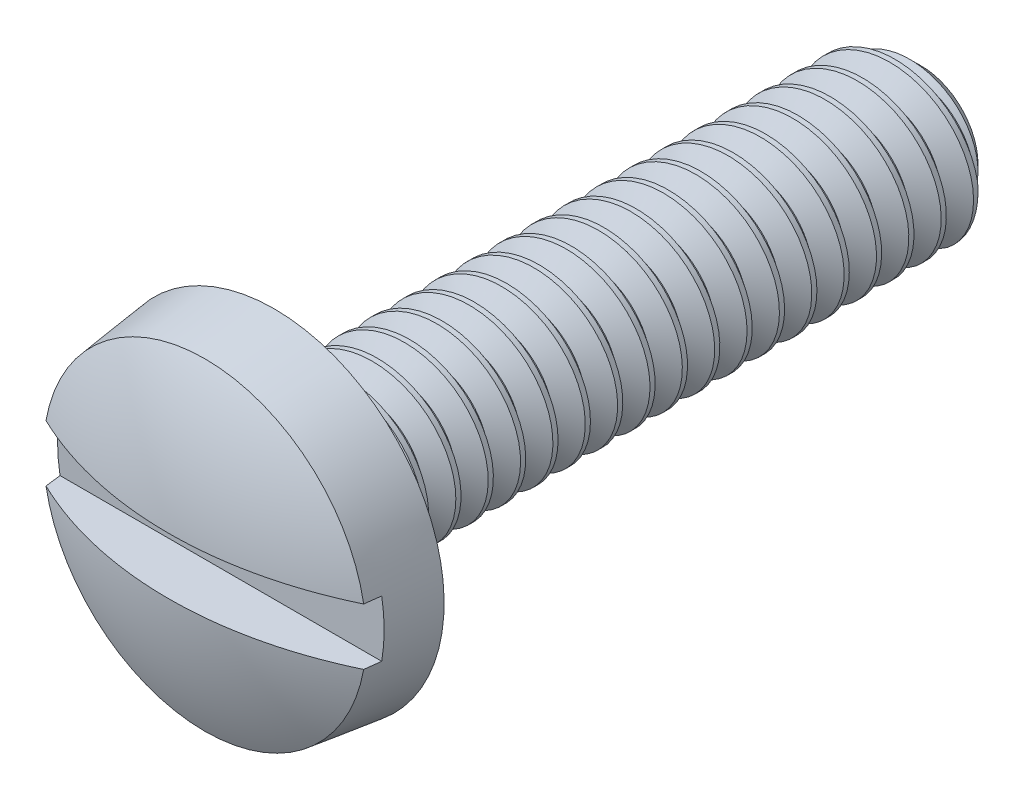
SolidWorks part; units mm, degrees
ref_plane "Front" through (0, 0, 0) normal (0, 0, 1) x (1, 0, 0)
ref_plane "Top" through (0, 0, 0) normal (0, 1, 0) x (1, 0, 0)
ref_plane "Right" through (0, 0, 0) normal (1, 0, 0) x (0, 0, -1)
sketch "Sketch1" plane through (0, 0, 0) normal (0, 0, 1) x (1, 0, 0)
  circle A0 centre (0, 0) radius 6.6675
  dimension "Head Dia" = 13.335
extrude "Extrude3" add sketch "Sketch1" along normal blind 4.191
sketch "Sketch11" plane through (0, 0, 0) normal (1, 0, 0) x (0, 0, -1)
  line L0 (0, 0) -> (-4.445, 0) construction
  line L3 (0, 6.6675) -> (-4.191, 6.6675) construction
  line L4 (-4.191, 6.6675) -> (-4.191, -6.6675) construction
  line L5 (-4.445, 6.9342) -> (0, 6.9342)
  line L7 (0, 6.9342) -> (0, 6.6675)
  line L8 (-2.7242, 6.333) -> (0, 6.6675)
  line L9 (0, -6.6675) -> (0, 6.6675) construction
  line L13 (-4.191, 0) -> (-4.445, 0)
  line L14 (-4.445, 0) -> (-4.445, 6.9342)
  arc A0 (-2.7242, 6.333) -> (-4.191, 0) centre (10.2136, 0) ccw
  dimension "D2" = 1.4668
  dimension "D1" = 7
  dimension "D3" = 0.254
  dimension "D5" = 0.2667
revolve "Cut-Revolve3" cut sketch "Sketch11" angle 360 about L0
sketch "Sketch4" plane through (0, 0, 0) normal (1, 0, 0) x (0, 0, -1)
  line L0 (0, 0) -> (25.4, 0)
  line L3 (25.4, 0) -> (25.4, 3.175)
  line L4 (25.4, 3.175) -> (0, 3.175)
  line L6 (0, 3.175) -> (0, 0)
  line L9 (25.4, 3.175) -> (25.4, -3.175) construction
  dimension "dia" = 6.35
  dimension "length" = 25.4
revolve "Revolve1" add sketch "Sketch4" angle 360 about L0
sketch "Sketch13" plane through (0, 0, -25.4) normal (0, 0, -1) x (-1, 0, 0)
  circle A2 centre (0, 0) radius 3.175
curve "Helix/Spiral1" pitch 1.27 height 29.591 radius 3.175 centre (0, 0, -25.4) axis (0, 0, 1) start towards (1, 0, 0)
chamfer "Chamfer2" distance 0.9525 angle 45 1 edges at (3.175, 0, -25.4)
sketch "Sketch14" plane through (0, 0, 0) normal (1, 0, 0) x (0, 0, -1)
  line L0 (25.4, 3.2147) -> (26.5112, 3.2147)
  line L1 (26.5112, 3.2147) -> (26.035, 2.3555)
  line L2 (26.035, 2.3555) -> (25.8762, 2.3555)
  line L3 (25.8762, 2.3555) -> (25.4, 3.2147)
  line L4 (25.6381, 2.7851) -> (26.2731, 2.7851) construction
  dimension "D1" = 0.1588
  dimension "D2" = 58
  dimension "D3" = 0.635
  dimension "D4" = 0.0397
sweep "Cut-Sweep1" cut profiles "Sketch14" path "Helix/Spiral1"
ref_plane "Plane1" through (0, 0, 12.7) normal (0, 0, -1) x (-1, 0, 0)
sketch "Sketch29" [suppressed] plane through (0, 0, 28.575) normal (0, 0, -1) x (-1, 0, 0)
  circle A0 centre (0, 0) radius 1.7526 construction
  circle A1 centre (0, 0) radius 1.7526
  point P3 (0, -1.7526)
  point P4 (0, 1.7526)
extrude "Extrude11" [suppressed] add sketch "Sketch29" against normal up to surface (28.575 mm away) up to plane "Front"
ref_plane "Plane2" through (0, 0, 4.191) normal (0, 0, 1) x (1, 0, 0)
sketch "Sketch26" plane through (0, 0, 0) normal (0, 0, 1) x (1, 0, 0)
  circle A1 centre (0, 0) radius 0.5461
  dimension "D1" = 1.0922
extrude "Extrude13" add sketch "Sketch26" along normal up to surface (4.1806 mm away)
sketch "Sketch31" plane through (0, 0, 4.191) normal (0, 0, 1) x (1, 0, 0)
  line L0 (-6.6675, 1.1112) -> (6.6675, -1.1112) construction
  line L1 (-6.6675, 1.1112) -> (6.6675, 1.1113)
  line L2 (-6.6675, 1.1112) -> (-6.6675, -1.1113)
  line L3 (-6.6675, -1.1113) -> (6.6675, -1.1112)
  line L4 (6.6675, 1.1113) -> (6.6675, -1.1112)
  circle A0 centre (0, 0) radius 6.6675 construction
  dimension "D1" = 2.2225
extrude "Extrude15" cut sketch "Sketch31" against normal blind 2.0955
sketch "Sketch18" plane through (0, 0, 0) normal (1, 0, 0) x (0, 0, -1)
  line L1 (25.4, 3.175) -> (0, 3.175) construction
  point P0 (23.495, -3.175)
  point P1 (24.13, 3.175)
  point P2 (-4.191, 1.1113)
  dimension "D1" = 1.27
  dimension "D2" = 1.905
equation "\"D3@Helix/Spiral1\" = \"Length@Sketch4\" + \"Head Ht@Extrude3\""
equation "\"D1@Sketch14\" = \"D4@Helix/Spiral1\" * .125"
equation "\"D3@Sketch14\" = \"D4@Helix/Spiral1\" * .5"
equation "\"D5@Sketch11\" = \"Head Dia@Sketch1\" * .02"
equation "\"D4@Sketch14\" = \"D1@Sketch14\" * .25"
equation "\"D1@Chamfer2\" = \"D4@Helix/Spiral1\" * .75"
equation "\"D1@Sketch18\" = \"D4@Helix/Spiral1\""
equation "\"D2@Sketch18\" = \"D4@Helix/Spiral1\" * 1.5"
equation "\"D1@Extrude15\" = \"Head Ht@Extrude3\" * .5"
equation "\"D2@Sketch11\" = \"Head Ht@Extrude3\" * .35"
equation "\"D1@Sketch31\" = \"D4@Helix/Spiral1\" * 1.75"
